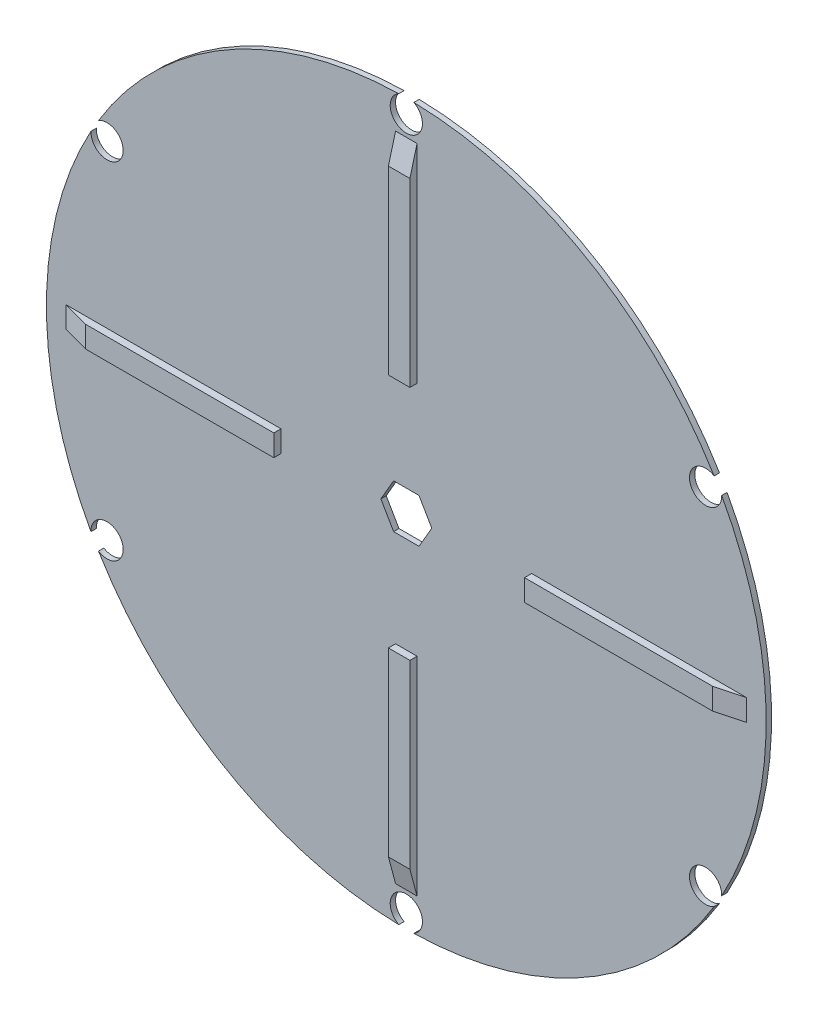
SolidWorks part; units mm, degrees
ref_plane "Front Plane" through (0, 0, 0) normal (0, 0, 1) x (1, 0, 0)
ref_plane "Top Plane" through (0, 0, 0) normal (0, 1, 0) x (1, 0, 0)
ref_plane "Right Plane" through (0, 0, 0) normal (1, 0, 0) x (0, 0, -1)
sketch "Sketch1" plane through (0, 0, 0) normal (0, 0, 1) x (1, 0, 0)
  circle A0 centre (0, 0) radius 100.5
  dimension "D1" = 201
extrude "Boss-Extrude1" add sketch "Sketch1" along normal blind 1.5 contours A0
sketch "Sketch8" plane through (0, 0, 0) normal (0, 0, -1) x (-1, 0, 0)
  text T0 "02-04-141118"
extrude "Cut-Extrude6" cut sketch "Sketch8" against normal blind 0.2
sketch "Sketch9" plane through (0, 0, 1.5) normal (0, 0, 1) x (1, 0, 0)
  line L1 (-7.1014, 0) -> (-3.5507, -6.15)
  line L2 (-3.5507, -6.15) -> (3.5507, -6.15)
  line L3 (3.5507, -6.15) -> (7.1014, 0)
  line L4 (7.1014, 0) -> (3.5507, 6.15)
  line L5 (3.5507, 6.15) -> (-3.5507, 6.15)
  line L6 (-3.5507, 6.15) -> (-7.1014, 0)
  circle A0 centre (0, 0) radius 6.15 construction
  dimension "D1" = 12.3
extrude "Cut-Extrude7" cut sketch "Sketch9" against normal blind 10
sketch "Sketch11" plane through (0, 0, 1.5) normal (0, 0, 1) x (1, 0, 0)
  line L0 (0, 0) -> (-95, 0)
  line L1 (-95, 0) -> (-95, 3)
  line L2 (-95, 3) -> (-35, 3)
  line L3 (-35, 3) -> (-35, -3)
  line L4 (-35, -3) -> (-95, -3)
  line L5 (-95, -3) -> (-95, 0)
  line L6 (0, 0) -> (0, 91)
  line L7 (0, 91) -> (-3, 91)
  line L8 (-3, 91) -> (-3, 33)
  line L9 (-3, 33) -> (3, 33)
  line L10 (3, 33) -> (3, 91)
  line L11 (3, 91) -> (0, 91)
  line L12 (35, 3) -> (95, 3)
  line L13 (35, -3) -> (35, 3)
  line L14 (95, -3) -> (35, -3)
  line L15 (95, 3) -> (95, 0)
  line L16 (95, 0) -> (95, -3)
  line L17 (3, -33) -> (-3, -33)
  line L18 (3, -91) -> (3, -33)
  line L19 (-3, -33) -> (-3, -91)
  line L20 (0, -91) -> (3, -91)
  line L21 (-3, -91) -> (0, -91)
  point P20 (0, 0)
  point P26 (0, 0)
  dimension "D1" = 3
  dimension "D2" = 6
  dimension "D3" = 6
  dimension "D4" = 3
  dimension "D5" = 95
  dimension "D6" = 60
  dimension "D7" = 91
  dimension "D8" = 58
  dimension "D9" = 2
  dimension "D10" = 2
extrude "Boss-Extrude2" add sketch "Sketch11" along normal blind 2 contours L7 L8 L9 L10 L11 | L1 L2 L3 L4 L5 | L14 L13 L12 L15 L16 | L19 L21 L20 L18 L17
chamfer "Chamfer1" distance 2 angle 75 4 edges at (95, 0, 3.5) (0, 91, 3.5) (0, -91, 3.5) (-95, 0, 3.5)
sketch "Sketch12" plane through (0, 0, 1.5) normal (0, 0, 1) x (1, 0, 0)
  circle A1 centre (0, 96.5) radius 4.5
  circle A2 centre (83.5715, 48.25) radius 4.5
  circle A3 centre (83.5715, -48.25) radius 4.5
  circle A4 centre (0, -96.5) radius 4.5
  circle A5 centre (-83.5715, -48.25) radius 4.5
  circle A6 centre (-83.5715, 48.25) radius 4.5
  point P19 (0, 0)
  dimension "D3" = 9
  dimension "D4" = 6
extrude "Cut-Extrude8" cut sketch "Sketch12" against normal blind 10
equation "\"1.5.00mm\"=3"
